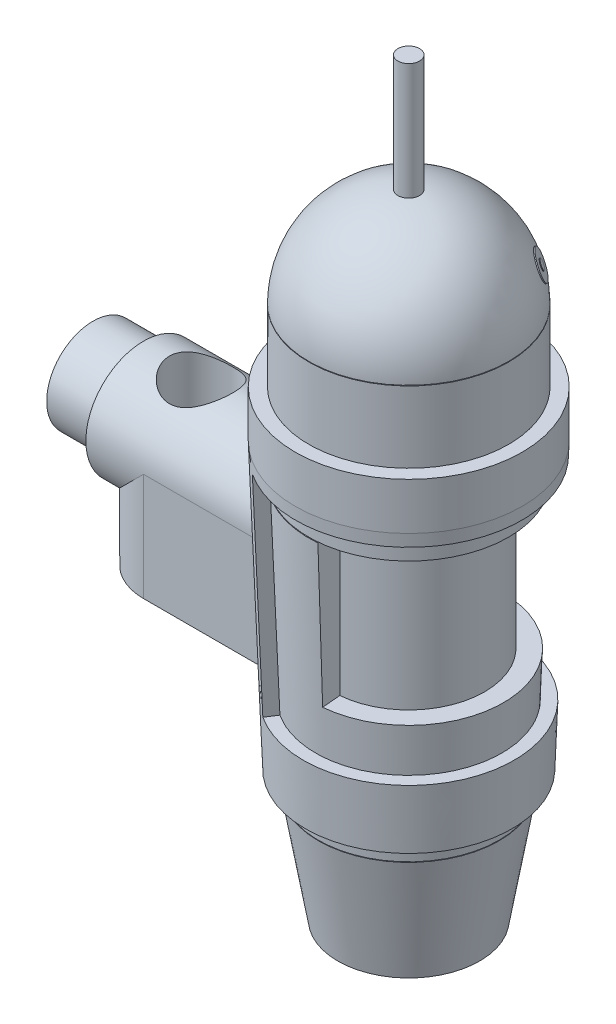
SolidWorks part; units mm, degrees
ref_plane "Front Plane" through (0, 0, 0) normal (0, 0, 1) x (1, 0, 0)
ref_plane "Top Plane" through (0, 0, 0) normal (0, 1, 0) x (1, 0, 0)
ref_plane "Right Plane" through (0, 0, 0) normal (1, 0, 0) x (0, 0, -1)
ref_axis "Axis1" through (0, -23.8831, 0) along (0, 1, 0)
sketch "Sketch1" plane through (0, 0, 0) normal (0, 0, 1) x (1, 0, 0)
  line L0 (11.5, 0) -> (14.65, 18.5)
  line L1 (14.65, 18.5) -> (16.2, 61.8)
  line L2 (16.2, 61.8) -> (16.2, 86.5)
  line L3 (11.5, 0) -> (10.5, 0)
  line L4 (10.5, 0) -> (10.5, 20)
  line L5 (10.5, 20) -> (6, 20)
  line L6 (6, 20) -> (6, 16.7)
  line L7 (6, 16.7) -> (0, 16.7)
  line L8 (0, 16.7) -> (0, 102.7)
  line L9 (0, 0) -> (0, -16.9601) construction
  arc A0 (16.2, 86.5) -> (0, 102.7) centre (0, 86.5) ccw
  dimension "D1" = 18.5
  dimension "D2" = 102.7
  dimension "D3" = 29.3
  dimension "D4" = 23
  dimension "D5" = 1
  dimension "D6" = 12
  dimension "D7" = 32.4
  dimension "D8" = 43.3
  dimension "D9" = 24.7
  dimension "D10" = 16.7
  dimension "D11" = 20
revolve "Revolve1" add sketch "Sketch1" angle 360 about L9
sketch "Sketch2" plane through (0, 0, 0) normal (0, 0, 1) x (1, 0, 0)
  line L0 (16.2, 61.8) -> (15.3552, 38.2)
  line L1 (14.65, 18.5) -> (16.2, 61.8) construction
  line L2 (15.3552, 38.2) -> (12.3, 38.2)
  line L3 (12.3, 38.2) -> (12.3, 61.8)
  line L4 (16.2, 61.8) -> (-16.2, 61.8) construction
  line L5 (12.3, 61.8) -> (16.2, 61.8)
  dimension "D1" = 3.9
  dimension "D2" = 23.6
revolve "Cut-Revolve1" cut sketch "Sketch2" angle 170 mid plane about L9
ref_plane "Plane4" through (0, 86.5, 0) normal (0, 1, 0) x (1, 0, 0)
sketch "Sketch10" plane through (0, 86.5, 0) normal (0, 1, 0) x (1, 0, 0)
  circle A0 centre (0, 0) radius 1.75
  dimension "D1" = 3.5
extrude "Boss-Extrude3" add sketch "Sketch10" along normal blind 35
ref_plane "Plane5" through (0, 0, 0) normal (0.7071, 0, 0.7071) x (0.7071, 0, -0.7071)
sketch "Sketch12" plane through (0, 0, 0) normal (0, 0, 1) x (1, 0, 0)
  line L0 (5, 16.7) -> (1.2, 17.7)
  line L1 (6, 16.7) -> (0, 16.7) construction
  line L2 (1.2, 17.7) -> (1.2, 18.2)
  line L3 (1.2, 18.2) -> (0, 18.2)
  line L4 (0, 16.7) -> (0, 102.7) construction
  line L5 (0, -23.8831) -> (0, 128.423) construction
  line L6 (5, 16.7) -> (0, 16.7)
  line L7 (0, 16.7) -> (0, 18.2)
  line L8 (0, 0) -> (0, 25.2847) construction
  dimension "D1" = 1.5
  dimension "D2" = 1.2
  dimension "D3" = 1
  dimension "D4" = 5
revolve "Cut-Revolve3" cut sketch "Sketch12" angle 360 about L8
sketch "Sketch14" plane through (0, 0, 0) normal (0, 0, 1) x (1, 0, 0)
  line L0 (16.2, 61.867) -> (15.95, 61.8)
  line L1 (15.95, 86.5) -> (16.7072, 86.5) construction
  line L2 (14.6516, 18.5441) -> (14.4016, 18.5)
  line L3 (16.2, 61.8) -> (16.2, 86.5) construction
  line L4 (14.65, 18.5) -> (16.2, 61.8) construction
  line L5 (1.4119, 61.8) -> (16.2, 61.8) construction
  line L6 (15.95, 61.8) -> (16.2, 61.733)
  line L7 (14.65, 18.5) -> (-14.65, 18.5) construction
  line L8 (15.95, 61.8) -> (17.09, 61.8) construction
  line L9 (16.2, 61.867) -> (16.2, 61.733)
  line L10 (16.2, 86.4559) -> (15.95, 86.5)
  line L11 (17.82, 86.5) -> (-17.82, 86.5) construction
  line L12 (15.95, 86.5) -> (16.2, 86.5441)
  line L13 (16.2, 86.5441) -> (16.2, 86.4559)
  line L14 (14.4016, 18.5) -> (14.6516, 18.4559)
  line L15 (14.4016, 18.5) -> (16.9577, 18.5) construction
  line L16 (14.6516, 18.5441) -> (14.6516, 18.4559)
  dimension "D1" = 30
  dimension "D2" = 0.25
  dimension "D3" = 20
  dimension "D4" = 20
  dimension "D5" = 0.25
revolve "Cut-Revolve4" cut sketch "Sketch14" angle 360 about L8
sketch "Sketch15" plane through (0, 20, 0) normal (0, -1, 0) x (1, 0, 0)
  line L0 (0, 0) -> (-21.6012, 0) construction
  line L1 (0, 0) -> (-6.8766, -4.9962) construction
  circle A0 centre (0, 0) radius 8.5 construction
  circle A1 centre (-6.8766, -4.9962) radius 1
  dimension "D2" = 2
  dimension "D3" = 17
  dimension "D1" = 36
extrude "Boss-Extrude4" add sketch "Sketch15" along normal blind 4
fillet "Fillet2" radius 1 1 edges at (-6.8766, 16, -5.9962)
pattern_circular "CirPattern1" count 10 over 360 about axis through (0, -23.8831, 0) along (0, 1, 0) skipping 1, 6 of "Boss-Extrude4", "Fillet2"
sketch "Sketch11" plane through (0, 0, 0) normal (0.7071, 0, 0.7071) x (0.7071, 0, -0.7071)
  line L0 (0, 86.5) -> (28.4481, 96.8543) construction
  line L1 (17.82, 86.5) -> (-17.82, 86.5) construction
  line L2 (15.0529, 89.5844) -> (15.9926, 89.9264)
  line L3 (15.9926, 89.9264) -> (15.4966, 91.289)
  line L4 (15.223, 92.0407) -> (14.2833, 91.6987)
  line L5 (14.2833, 91.6987) -> (15.0529, 89.5844)
  line L6 (15.4966, 91.289) -> (15.5906, 91.3232)
  line L7 (15.5906, 91.3232) -> (15.317, 92.0749)
  line L8 (15.317, 92.0749) -> (15.223, 92.0407)
  line L9 (15.4966, 91.289) -> (15.223, 92.0407) construction
  arc A0 (16.1999, 86.5441) -> (1.75, 102.6052) centre (0, 86.5) ccw construction
  dimension "D1" = 20
  dimension "D2" = 1
  dimension "D3" = 4.5
  dimension "D4" = 1.6
  dimension "D5" = 0.1
revolve "Revolve3" add sketch "Sketch11" angle 360 about L0
ref_plane "focus plan min" through (0, -2.3, 0) normal (0, -1, 0) x (1, 0, 0)
ref_plane "Plane1" through (0, 33.5, 0) normal (0, 1, 0) x (-1, 0, 0)
sketch "Sketch3" plane through (0, 0, 0) normal (0, 0, 1) x (1, 0, 0)
  line L0 (16.75, 21.2) -> (18.4, 67.2935)
  line L1 (18.4, 67.2935) -> (18.4, 74.9)
  line L2 (18.4, 74.9) -> (16.2, 74.9)
  line L5 (14.7467, 21.2) -> (16.75, 21.2)
  line L6 (0, 0) -> (0, 123.1204) construction
  line L7 (14.65, 18.5) -> (16.2, 61.8) construction
  line L8 (16.2, 74.9) -> (16.2, 61.8)
  line L9 (16.2, 61.8) -> (16.2, 86.5) construction
  line L10 (16.2, 61.8) -> (14.7467, 21.2)
  dimension "D1" = 33.5
  dimension "D2" = 36.8
  dimension "D3" = 53.7
  dimension "D4" = 21.2
revolve "Revolve2" add sketch "Sketch3" angle 360 about L6
sketch "Sketch4" plane through (0, 0, 0) normal (0, 0, 1) x (1, 0, 0)
  line L0 (18.4, 65.3) -> (5, 65.3)
  line L1 (5, 65.3) -> (5, 31)
  line L2 (5, 31) -> (18.4, 31)
  line L3 (18.4, 31) -> (18.4, 65.3)
  line L4 (-16.75, 21.2) -> (16.75, 21.2) construction
  line L5 (0, 16.7) -> (0, 102.7) construction
  line L6 (18.4, 67.2935) -> (18.4, 74.9) construction
  dimension "D1" = 34.3
  dimension "D2" = 9.8
  dimension "D3" = 5
revolve "Cut-Revolve2" cut sketch "Sketch4" angle 246 mid plane about L8
ref_plane "Plane2" through (-43, 0, 0) normal (1, 0, 0) x (0, 0, -1)
sketch "Sketch6" plane through (-43, 0, 0) normal (1, 0, 0) x (0, 0, -1)
  line L0 (0, 18.5) -> (0, 61.8) construction
  line L1 (-11.5, 0) -> (11.5, 0) construction
  line L2 (9.35, 50.45) -> (9.35, 33)
  line L3 (9.35, 33) -> (-9.35, 33)
  line L4 (-9.35, 50.45) -> (-9.35, 33)
  arc A0 (9.35, 50.45) -> (-9.35, 50.45) centre (0, 50.45) ccw
  point P7 (0, 59.8)
  dimension "D1" = 26.8
  dimension "D2" = 18.7
  dimension "D3" = 33
extrude "Boss-Extrude1" add sketch "Sketch6" along normal up to surface (28.5962 mm away)
fillet "Fillet1" radius 9.35 3 edges at (-43, 41.725, -9.35) (-43, 33, 0) (-43, 41.725, 9.35)
sketch "Sketch7" plane through (0, 33, 0) normal (0, -1, 0) x (1, 0, 0)
  line L0 (0, 0) -> (-33.65, 0) construction
  circle A0 centre (-33.65, 0) radius 5.15
  arc A1 (-33.65, 9.35) -> (-33.65, -9.35) centre (-33.65, 0) ccw construction
  circle A2 centre (0, 0) radius 14.7467 construction
  circle A3 centre (0, 0) radius 14.7467 construction
  point P7 (-28.5, 0)
  point P11 (-14.7467, 0)
  dimension "D1" = 10.3
  dimension "D2" = 13.7533
extrude "Cut-Extrude1" cut sketch "Sketch7" against normal through all
ref_plane "Plane3" through (-51.2, 0, 0) normal (1, 0, 0) x (0, 0, -1)
sketch "Sketch9" plane through (-51.2, 0, 0) normal (1, 0, 0) x (0, 0, -1)
  line L1 (0, 18.5) -> (0, 61.8) construction
  line L2 (-9.35, 33) -> (9.35, 33) construction
  circle A0 centre (0, 51) radius 7.5
  dimension "D1" = 15
  dimension "D2" = 18
extrude "Boss-Extrude2" add sketch "Sketch9" along normal up to surface (11.9667 mm away)
ref_plane "Focus at 20X" through (0, -60.96, 0) normal (0, -1, 0) x (-1, 0, 0)
ref_plane "Focus at 30X" through (0, -24.13, 0) normal (0, -1, 0) x (-1, 0, 0)
ref_plane "Focus at 50X" through (0, -3.81, 0) normal (0, -1, 0) x (-1, 0, 0)
ref_plane "Focus at 200X" through (0, 0, 0) normal (0, -1, 0) x (-1, 0, 0)
ref_plane "Focus at 230X" through (0, -1.6002, 0) normal (0, -1, 0) x (-1, 0, 0)
